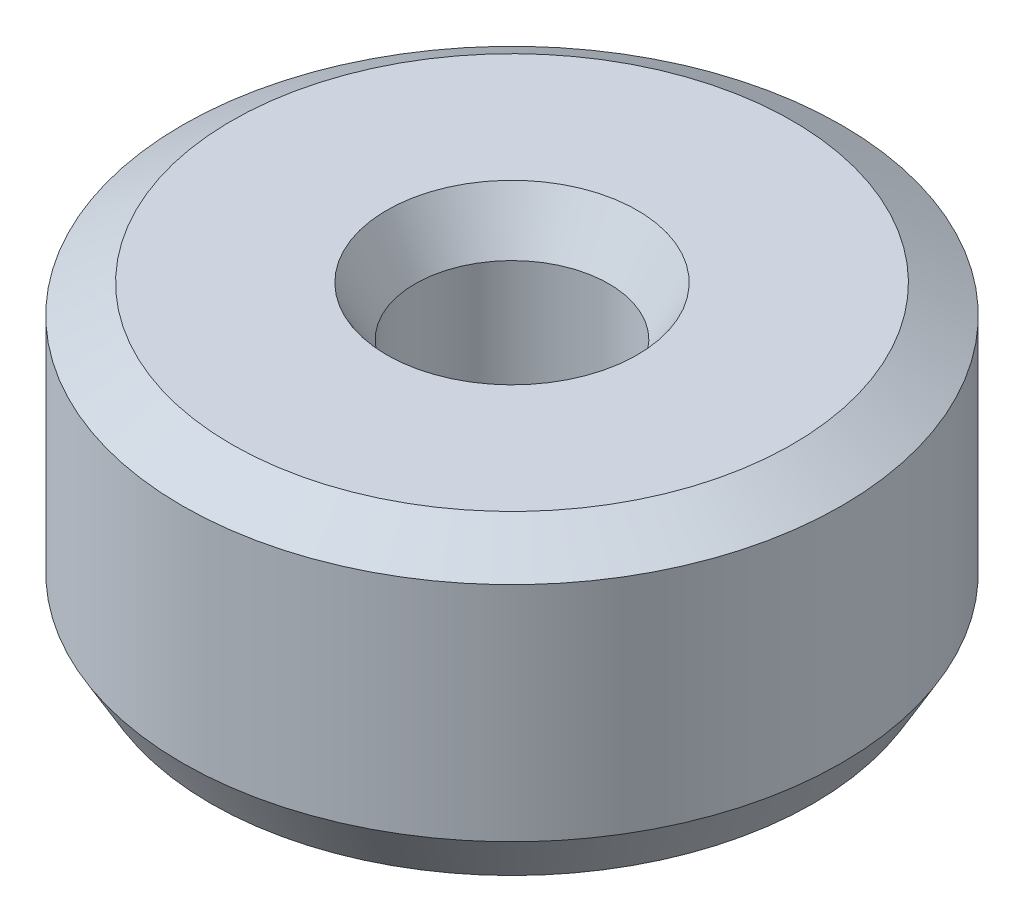
SolidWorks part; units mm, degrees
ref_plane "Front Plane" through (0, 0, 0) normal (0, 0, 1) x (1, 0, 0)
ref_plane "Top Plane" through (0, 0, 0) normal (0, 1, 0) x (1, 0, 0)
ref_plane "Right Plane" through (0, 0, 0) normal (1, 0, 0) x (0, 0, -1)
sketch "Sketch1" plane through (0, 0, 0) normal (0, 1, 0) x (1, 0, 0)
  circle A0 centre (0, 0) radius 7.5
  dimension "SLEEVE_OD" = 15
extrude "Boss-Extrude1" add sketch "Sketch1" along normal blind 6.837
sketch "Sketch2" plane through (0, 0, 0) normal (0, 1, 0) x (1, 0, 0)
  circle A0 centre (0, 0) radius 2.2019
  dimension "BORE_D" = 4.4038
extrude "Cut-Extrude1" cut sketch "Sketch2" along normal through all
chamfer "Chamfer1" distance 0.6484 angle 60 4 edges at (0, 6.837, 2.2019) (0, 0, 2.2019) (0, 0, 7.5) (0, 6.837, 7.5) first distance on face at (0, 6.837, 2.2019) first distance on face at (0, 0, 2.2019) first distance on face at (0, 6.837, 7.5)
